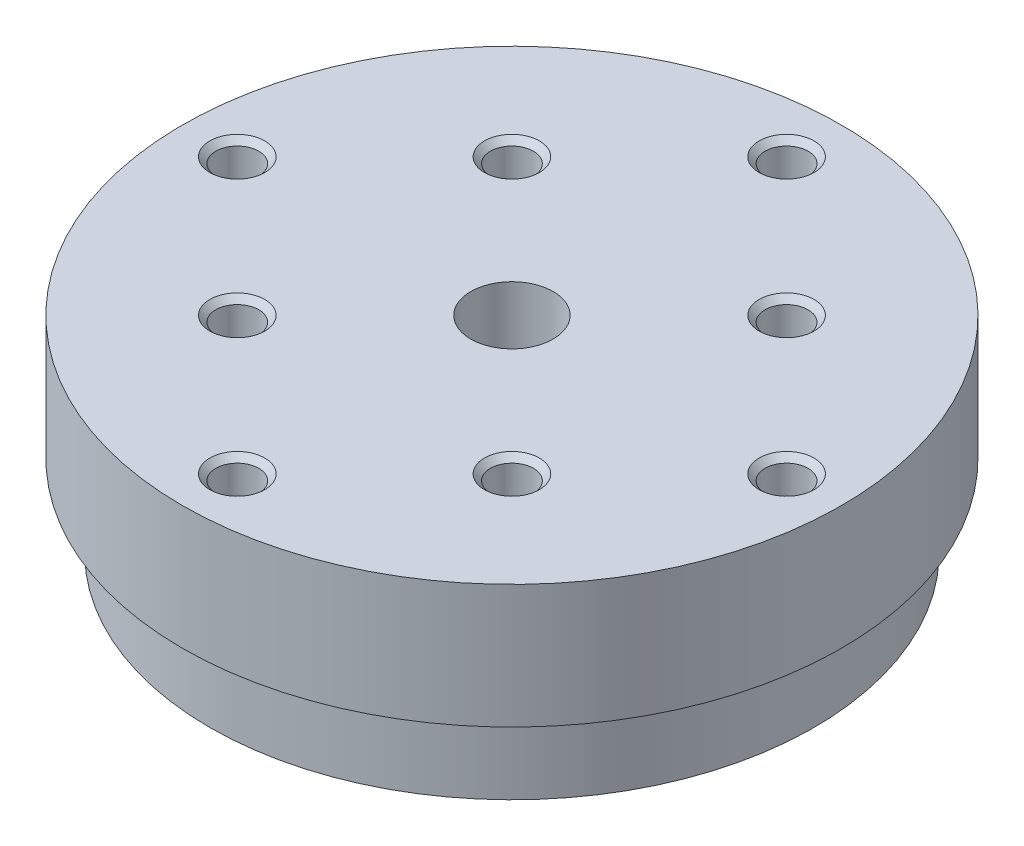
SolidWorks part; units mm, degrees
ref_plane "前视基准面" through (0, 0, 0) normal (0, 0, 1) x (1, 0, 0)
ref_plane "上视基准面" through (0, 0, 0) normal (0, 1, 0) x (1, 0, 0)
ref_plane "右视基准面" through (0, 0, 0) normal (1, 0, 0) x (0, 0, -1)
sketch "草图1" plane through (0, 0, 0) normal (0, 0, 1) x (1, 0, 0)
  line L0 (0, 4.5) -> (12, 4.5)
  line L1 (12, 4.5) -> (12, 0)
  line L2 (12, 0) -> (11, 0)
  line L3 (11, 0) -> (11, -3)
  line L4 (11, -3) -> (0, -3)
  line L5 (0, -3) -> (0, 4.5)
  line L6 (0, -3) -> (0, 4.5) construction
revolve "旋转1" add sketch "草图1" angle 360 about L6 reverse direction yes
ref_plane "基准面4" through (0, 3.5, 0) normal (0, 1, 0) x (1, 0, 0)
sketch "草图2" plane through (0, 0, 0) normal (0, 0, 1) x (1, 0, 0)
  line L0 (0, 4.5) -> (1.5, 4.5)
  line L1 (1.5, 4.5) -> (1.5, -10.5)
  line L2 (1.5, -10.5) -> (0, -10.5)
  line L3 (0, -10.5) -> (0, 4.5)
  line L4 (0, -10.5) -> (0, 4.5) construction
revolve "切除-旋转1" cut sketch "草图2" angle 360 about L4 reverse direction yes
ref_plane "基准面5" through (0, 4.5, 0) normal (0, 1, 0) x (1, 0, 0)
sketch "草图3" plane through (0, 0, 0) normal (0, 0, 1) x (1, 0, 0)
  line L0 (10, 4.5) -> (11, 4.5)
  line L1 (11, 4.5) -> (10.7835, 4.2835)
  line L2 (10.7835, 4.2835) -> (10.7835, 1.2024)
  line L3 (10.7835, 1.2024) -> (10, 0.75)
  line L4 (10, 0.75) -> (10, 4.5)
  line L5 (10, 0.75) -> (10, 4.5) construction
revolve "切除-旋转2" cut sketch "草图3" angle 360 about L5 reverse direction yes
cosmetic thread "装饰螺纹线1" parameters "D1"=3, "D2"=2
sketch "草图4" plane through (0, 0, 0) normal (0, 1, 0) x (1, 0, 0)
  line L0 (10, 0) -> (-697.1068, 707.1068)
  line L1 (10, 0) -> (-697.1068, -707.1068)
pattern_linear "阵列(线性)1" count 3 spacing 7.0711 along (-0.7071, 0, -0.7071) count 3 spacing 7.0711 along (-0.7071, 0, 0.7071) skipping (1, 1) of "切除-旋转2"
ref_plane "b_to_a XY" through (0, 0, 0) normal (0, 1, 0) x (1, 0, 0)
ref_plane "b_to_a XZ" through (0, 0, 0) normal (0, 0, 1) x (1, 0, 0)
ref_plane "b_to_a YZ" through (0, 0, 0) normal (1, 0, 0) x (0, 0, -1)
ref_axis "b_to_a X" through (-80.9, 0, 0) along (1, 0, 0)
ref_axis "b_to_a Y" through (0, 0, 50) along (0, 0, -1)
ref_axis "b_to_a Z" through (0, 50, 0) along (0, -1, 0)
sketch3d "b_to_a"
  point P0 (0, 0, 0)
